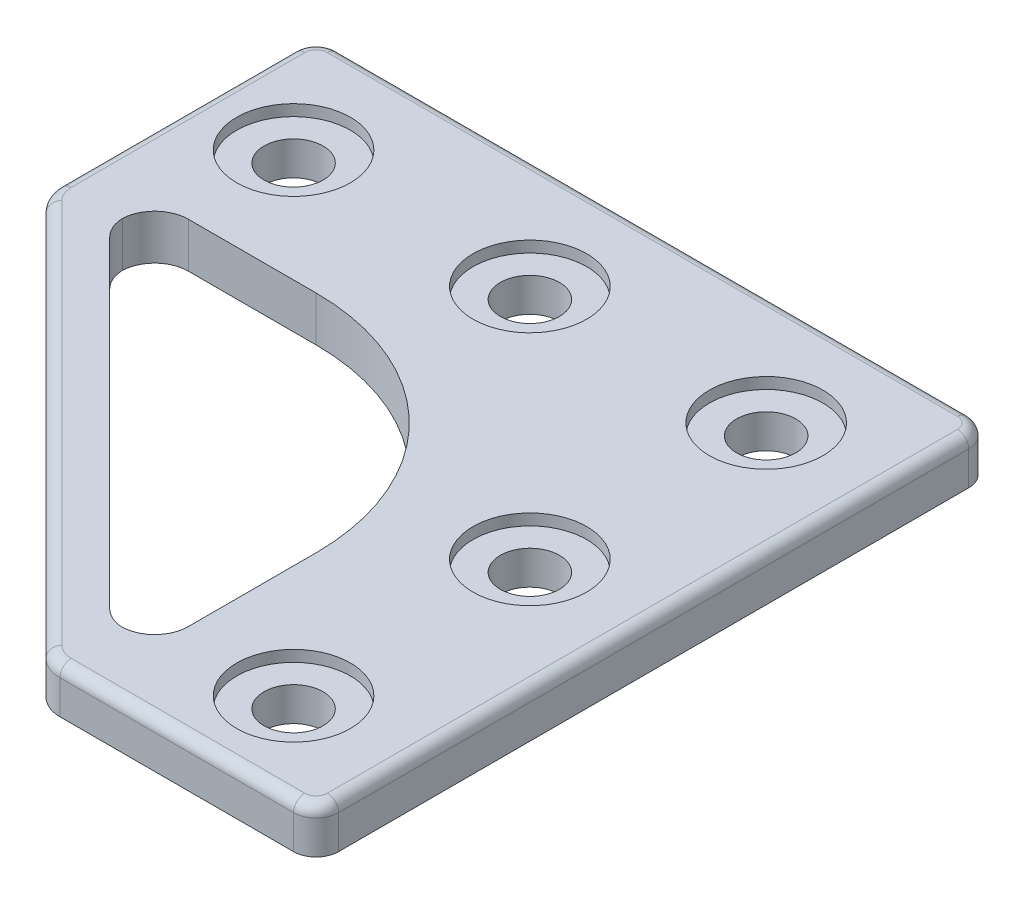
SolidWorks part; units mm, degrees
ref_plane "Front Plane" through (0, 0, 0) normal (0, 0, 1) x (1, 0, 0)
ref_plane "Top Plane" through (0, 0, 0) normal (0, 1, 0) x (1, 0, 0)
ref_plane "Right Plane" through (0, 0, 0) normal (1, 0, 0) x (0, 0, -1)
sketch "Sketch1" plane through (0, 0, 0) normal (0, 1, 0) x (1, 0, 0)
  line L0 (-32, 10) -> (10, 10) construction
  line L2 (0, 0) -> (0, -34.3431)
  line L3 (2, -40) -> (18, -40)
  line L4 (20, -10.1754) -> (20, -38)
  line L5 (0, 0) -> (-34.3431, 0)
  line L6 (20, -10.1754) -> (20, 18)
  line L7 (18, 20) -> (-38, 20)
  line L8 (-40, 2) -> (-40, 18)
  line L9 (10, -32) -> (10, -11) construction
  line L10 (-40, 2) -> (-40, -4)
  line L11 (-40, -4) -> (-4, -40)
  line L12 (-4, -40) -> (2, -40)
  line L13 (-34.3431, 0) -> (-34.3431, -4)
  line L14 (-34.3431, -4) -> (-4, -34.3431)
  line L15 (-4, -34.3431) -> (0, -34.3431)
  circle A0 centre (-32, 10) radius 2.625
  circle A1 centre (-11, 10) radius 2.625
  circle A4 centre (10, -32) radius 2.625
  circle A5 centre (10, 10) radius 2.625
  circle A6 centre (10, -11) radius 2.625
  arc A8 (20, -38) -> (18, -40) centre (18, -38) cw
  arc A10 (20, 18) -> (18, 20) centre (18, 18) ccw
  arc A12 (-38, 20) -> (-40, 18) centre (-38, 18) ccw
  point P12 (-40, 10)
  point P30 (-40, 0)
  point P33 (-40, 20)
  point P36 (-22, -22)
  dimension "D7" = 5.25
  dimension "D8" = 2
  dimension "D1" = 20
  dimension "D2" = 40
  dimension "D3" = 10
  dimension "D4" = 8
  dimension "D5" = 21
  dimension "D6" = 21
  dimension "D9" = 21
  dimension "D10" = 4
  dimension "D11" = 4
  dimension "D12" = 4
  dimension "D13" = 10
extrude "Boss-Extrude1" add sketch "Sketch1" along normal blind 4
fillet "Fillet1" radius 20 1 edges at (0, 2, 0)
fillet "Fillet2" radius 3 6 edges at (-40, 2, 4) (-4, 2, 40) (-4, 2, 34.3431) (0, 2, 34.3431) (-34.3431, 2, 4) (-34.3431, 2, 0)
sketch "Sketch2" plane through (0, 4, 0) normal (0, 1, 0) x (1, 0, 0)
  circle A0 centre (-32, 10) radius 5.05
  circle A1 centre (-11, 10) radius 5.05
  circle A2 centre (10, 10) radius 5.05
  circle A3 centre (10, -11) radius 5.05
  circle A4 centre (10, -32) radius 5.05
  circle A5 centre (-32, 10) radius 2.625 construction
  circle A6 centre (-11, 10) radius 2.625 construction
  circle A7 centre (10, 10) radius 2.625 construction
  circle A8 centre (10, -11) radius 2.625 construction
  circle A9 centre (10, -32) radius 2.625 construction
  dimension "D1" = 10.1
extrude "Cut-Extrude1" cut sketch "Sketch2" against normal blind 1
fillet "Fillet3" radius 1 10 edges at (19.4142, 4, -19.4142) (20, 4, 10) (19.4142, 4, 39.4142) (7.6213, 4, 40) (-3.9054, 4, 39.7716) (-22, 4, 22) (-39.7716, 4, 3.9054) (-40, 4, -7.6213) (-39.4142, 4, -19.4142) (-10, 4, -20)
